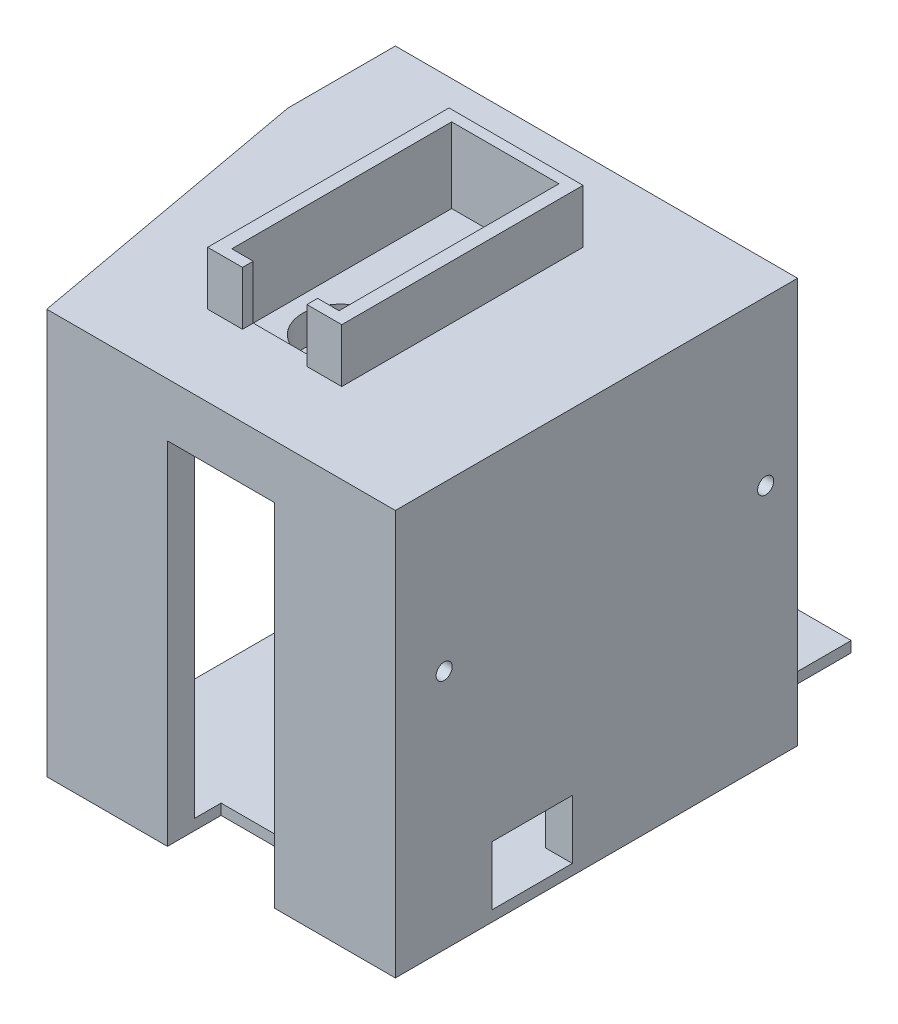
SolidWorks part; units mm, degrees
ref_plane "Front Plane" through (0, 0, 0) normal (0, 0, 1) x (1, 0, 0)
ref_plane "Top Plane" through (0, 0, 0) normal (0, 1, 0) x (1, 0, 0)
ref_plane "Right Plane" through (0, 0, 0) normal (1, 0, 0) x (0, 0, -1)
sketch "Sketch1" plane through (0, 0, 0) normal (0, 1, 0) x (1, 0, 0)
  line L1 (0, 0) -> (55, 0)
  line L2 (0, 0) -> (0, 65)
  line L3 (0, 65) -> (55, 65)
  line L4 (55, 0) -> (55, 65)
  dimension "D1" = 55
  dimension "D2" = 65
extrude "Base" add sketch "Sketch1" along normal blind 2
sketch "Sketch2" plane through (0, 2, 0) normal (0, 1, 0) x (1, 0, 0)
  line L0 (0, 0) -> (55, 0) construction
  line L2 (55, 65) -> (0, 65) construction
  circle A0 centre (3, 3.5) radius 1.2
  circle A1 centre (52, 3.5) radius 1.2
  circle A2 centre (3, 61.5) radius 1.2
  circle A3 centre (52, 61.5) radius 1.2
  point P12 (27.5, 0)
  dimension "D1" = 2.4
  dimension "D2" = 24.5
  dimension "D3" = 24.5
  dimension "D4" = 58
  dimension "D5" = 3.5
extrude "PiMountScrewHoles" cut sketch "Sketch2" against normal up to surface (2 mm away) up to face at (27.5, 0, -32.5)
sketch "Sketch3" plane through (0, 0, 0) normal (-1, 0, 0) x (0, 0, 1)
  line L0 (-65, 0) -> (0, 0) construction
  line L1 (-65, 2) -> (-45, 2)
  line L2 (-65, 2) -> (-65, 0)
  line L3 (-65, 0) -> (-45, 0)
  line L4 (-45, 2) -> (-45, 0)
  dimension "D1" = 20
extrude "PlateLegExt-1" add sketch "Sketch3" along normal blind 10
sketch "Sketch19" plane through (0, 0, -65) normal (0, 0, -1) x (-1, 0, 0)
  line L1 (-55, 2) -> (0, 2)
  line L2 (-55, 2) -> (-55, 0)
  line L3 (-55, 0) -> (0, 0)
  line L4 (0, 2) -> (0, 0)
extrude "PiFrontBase" add sketch "Sketch19" along normal blind 20
sketch "Sketch21" plane through (55, 0, 0) normal (1, 0, 0) x (0, 0, -1)
  line L0 (0, 0) -> (85, 0) construction
  line L1 (0, 2) -> (65, 2)
  line L2 (0, 2) -> (0, 0)
  line L3 (0, 0) -> (65, 0)
  line L4 (65, 2) -> (65, 0)
extrude "BatteryWall-Ext" add sketch "Sketch21" along normal blind 10
sketch "Sketch22" plane through (0, 0, 0) normal (0, 0, 1) x (1, 0, 0)
  line L0 (0, 0) -> (65, 0) construction
  line L1 (0, 2) -> (22.5, 2)
  line L2 (0, 2) -> (0, 0)
  line L3 (0, 0) -> (22.5, 0)
  line L4 (22.5, 2) -> (22.5, 0)
  line L6 (42.5, 2) -> (55, 2)
  line L7 (42.5, 2) -> (42.5, 0)
  line L8 (42.5, 0) -> (55, 0)
  line L11 (0, 2) -> (65, 2) construction
  line L12 (55, 2) -> (55, 0)
  line L13 (55, 0) -> (55, 2) construction
  point P16 (32.5, 0)
  dimension "D1" = 10
  dimension "D2" = 20
extrude "PlateLegExt-2" add sketch "Sketch22" along normal blind 10
sketch "Sketch30" plane through (55, 0, 0) normal (1, 0, 0) x (0, 0, -1)
  line L1 (-10, 2) -> (0, 2)
  line L2 (-10, 2) -> (-10, 0)
  line L3 (-10, 0) -> (0, 0)
  line L4 (0, 2) -> (0, 0)
extrude "CornerExtension" add sketch "Sketch30" along normal up to vertex (10 mm away) up to point (65, 2, 0)
sketch "Sketch23" plane through (0, 2, 0) normal (0, 1, 0) x (1, 0, 0)
  line L0 (65, 65) -> (55, 65) construction
  line L2 (22.5, -5) -> (0, -5)
  line L3 (22.5, -5) -> (22.5, -10)
  line L4 (-5, 65) -> (-10, 65)
  line L8 (60, 65) -> (65, 65)
  line L9 (60, 65) -> (60, -5)
  line L11 (65, 65) -> (65, -10)
  line L14 (-5, 65) -> (-5, 45)
  line L15 (-5, 45) -> (-10, 45)
  line L16 (-10, 65) -> (-10, 45)
  line L21 (22.5, -10) -> (0, -10)
  line L22 (0, -5) -> (0, -10)
  line L23 (22.5, -10) -> (22.5, 0) construction
  line L24 (0, 65) -> (-10, 65) construction
  line L25 (42.5, -10) -> (42.5, 0) construction
  line L26 (42.5, -10) -> (65, -10)
  line L27 (42.5, -10) -> (42.5, -5)
  line L30 (65, 65) -> (65, -10) construction
  line L31 (65, -10) -> (42.5, -10) construction
  line L32 (42.5, -5) -> (60, -5)
extrude "PlateLegs" add sketch "Sketch23" along normal blind 63.5
sketch "Sketch29" plane through (65, 0, 0) normal (1, 0, 0) x (0, 0, -1)
  line L0 (-10, 0) -> (65, 0) construction
  circle A0 centre (59.045, 45) radius 1.5
  circle A1 centre (-0.905, 45) radius 1.5
  point P8 (27.5, 0)
  dimension "D1" = 3
  dimension "D2" = 59.95
  dimension "D3" = 31.545
  dimension "D4" = 45
extrude "Battery-ScrewHoles" cut sketch "Sketch29" against normal up to surface (5 mm away) up to face at (60, 33.75, -30)
sketch "Sketch24" plane through (0, 65.5, 0) normal (0, 1, 0) x (1, 0, 0)
  line L7 (0, -10) -> (65, -10)
  line L8 (42.5, -10) -> (65, -10) construction
  line L9 (65, -10) -> (65, 65)
  line L10 (65, 65) -> (-10, 65)
  line L11 (-10, 65) -> (-10, 45)
  line L12 (-10, 45) -> (0, -10)
extrude "RotatorPlate" add sketch "Sketch24" along normal blind 10
sketch "Sketch25" plane through (0, 75.5, 0) normal (0, 1, 0) x (1, 0, 0)
  line L2 (37.5, 7) -> (37.5, 48)
  line L4 (17.5, 7) -> (17.5, 48)
  line L7 (37.5, 48) -> (17.5, 48)
  line L8 (17.5, 7) -> (37.5, 7)
  line L9 (65, -10) -> (65, 65) construction
  line L11 (65, 65) -> (-10, 65) construction
  point P8 (27.5, 65)
  point P9 (65, 27.5)
  point P10 (37.5, 27.5)
  point P11 (27.5, 48)
  dimension "D1" = 41
  dimension "D2" = 20
extrude "Inset-Servo" cut sketch "Sketch25" against normal blind 4
sketch "Sketch26" plane through (0, 71.5, 0) normal (0, 1, 0) x (1, 0, 0)
  line L0 (17.5, 7) -> (37.5, 7) construction
  line L3 (37.5, 48) -> (17.5, 48) construction
  circle A0 centre (27.5, 17.25) radius 1.5
  point P8 (27.5, 48)
  dimension "D1" = 3
  dimension "D2" = 10.25
extrude "Hole-ServoScrew" cut sketch "Sketch26" against normal up to surface (6 mm away) up to face at (20.9091, 65.5, -15.4545)
sketch "Sketch27" plane through (0, 71.5, 0) normal (0, 1, 0) x (1, 0, 0)
  circle A0 centre (27.5, 17.25) radius 7
  circle A1 centre (27.5, 17.25) radius 1.5 construction
  dimension "D1" = 14
extrude "Inset-ServoAxle" cut sketch "Sketch27" against normal blind 5.8
sketch "Sketch28" plane through (0, 75.5, 0) normal (0, 1, 0) x (1, 0, 0)
  line L2 (37.5, 7) -> (37.5, 48)
  line L4 (17.5, 7) -> (17.5, 48)
  line L6 (40, 5) -> (40, 50)
  line L8 (15, 5) -> (15, 50)
  line L11 (37.5, 7) -> (37.5, 48) construction
  line L18 (17.5, 48) -> (17.5, 7) construction
  line L19 (15, 5) -> (21.5, 5)
  line L24 (21.5, 5) -> (21.5, 7)
  line L25 (17.5, 7) -> (37.5, 7) construction
  line L26 (40, 5) -> (33.5, 5)
  line L27 (33.5, 5) -> (33.5, 7)
  line L28 (17.5, 7) -> (37.5, 7) construction
  line L29 (33.5, 7) -> (37.5, 7)
  line L30 (17.5, 7) -> (21.5, 7)
  line L31 (17.5, 48) -> (37.5, 48)
  line L32 (15, 50) -> (40, 50)
  line L33 (37.5, 48) -> (17.5, 48) construction
  point P15 (27.5, 7)
  point P20 (40, 27.5)
  point P21 (37.5, 27.5)
  dimension "D7" = 6
  dimension "D1" = 2.5
  dimension "D3" = 45
  dimension "D4" = 25
  dimension "D8" = 12
extrude "RetainingWalls-Servo" add sketch "Sketch28" along normal blind 10
sketch "Sketch31" plane through (60, 0, 0) normal (-1, 0, 0) x (0, 0, 1)
  line L0 (-65, 2) -> (5, 2) construction
  line L1 (-23, 13) -> (-8, 13)
  line L2 (-23, 13) -> (-23, 2)
  line L3 (-23, 2) -> (-8, 2)
  line L4 (-8, 13) -> (-8, 2)
  line L5 (5, 65.5) -> (5, 2) construction
  dimension "D1" = 15
  dimension "D2" = 11
  dimension "D3" = 13
extrude "Power-Hole" cut sketch "Sketch31" against normal up to surface (5 mm away) up to face at (65, 45, -60.545)
equation "\"PlateLegExtent\"= 10mm"
equation "\"D1@PlateLegExt-1\" = \"PlateLegExtent\""
equation "\"PlateLegHeight\"= 2.5in"
equation "\"D1@BatteryWall-Ext\" = \"PlateLegExtent\""
equation "\"D1@PlateLegExt-2\" = \"PlateLegExtent\""
equation "\"D1@PlateLegs\" = \"PlateLegHeight\""
